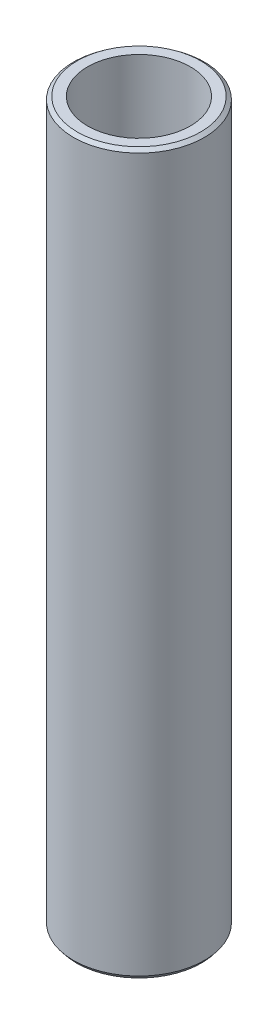
SolidWorks part; units mm, degrees
ref_plane "Front Plane" through (0, 0, 0) normal (0, 0, 1) x (1, 0, 0)
ref_plane "Top Plane" through (0, 0, 0) normal (0, 1, 0) x (1, 0, 0)
ref_plane "Right Plane" through (0, 0, 0) normal (1, 0, 0) x (0, 0, -1)
sketch "Sketch1" plane through (0, 0, 0) normal (0, 1, 0) x (1, 0, 0)
  circle A0 centre (0, 0) radius 37.5
  dimension "SHAFT_OD" = 75
extrude "Boss-Extrude1" add sketch "Sketch1" along normal blind 412.2638
sketch "Sketch2" plane through (0, 0, 0) normal (0, 1, 0) x (1, 0, 0)
  circle A0 centre (0, 0) radius 29.4401
  dimension "BORE_D" = 58.8801
extrude "Cut-Extrude1" cut sketch "Sketch2" along normal through all
chamfer "Chamfer1" distance 1.6494 angle 52.3 2 edges at (0, 412.2638, 37.5) (0, 0, 37.5) first distance on face at (0, 412.2638, 37.5) first distance on face at (0, 0, 29.4401)
